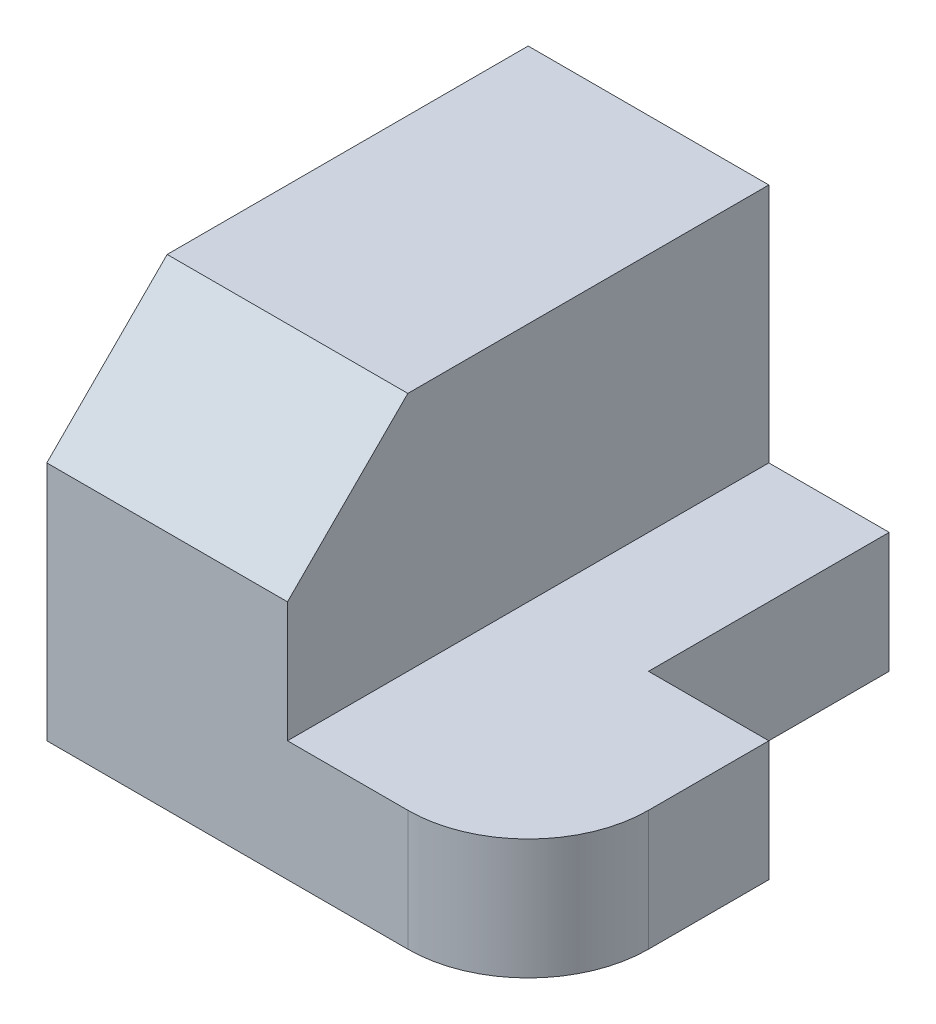
SolidWorks part; units mm, degrees
ref_plane "前基準面" through (0, 0, 0) normal (0, 0, 1) x (1, 0, 0)
ref_plane "上基準面" through (0, 0, 0) normal (0, 1, 0) x (1, 0, 0)
ref_plane "右基準面" through (0, 0, 0) normal (1, 0, 0) x (0, 0, -1)
sketch "草圖1" plane through (0, 0, 0) normal (0, 1, 0) x (1, 0, 0)
  line L1 (5, 10) -> (-5, 10)
  line L2 (5, 10) -> (5, -10)
  line L3 (5, -10) -> (-5, -10)
  line L4 (-5, 10) -> (-5, -10)
  line L5 (5, 10) -> (-5, -10) construction
  line L6 (5, -10) -> (-5, 10) construction
  line L7 (5, 10) -> (10, 10)
  line L8 (5, 10) -> (5, -10)
  line L9 (5, -10) -> (10, -10)
  line L10 (15, 0) -> (15, -5)
  line L13 (15, 0) -> (10, 0)
  line L14 (10, 10) -> (10, 0)
  line L15 (5, -10) -> (-5, -10)
  line L16 (5, -10) -> (5, -5)
  line L17 (5, -5) -> (-5, -5)
  line L18 (-5, -10) -> (-5, -5)
  arc A0 (15, -5) -> (10, -10) centre (10, -5) cw
  point P0 (0, 0)
  dimension "D7" = 5
  dimension "D1" = 20
  dimension "D2" = 10
  dimension "D3" = 10
  dimension "D4" = 5
  dimension "D5" = 10
  dimension "D6" = 5
extrude "填料-伸長1" add sketch "草圖1" along normal blind 5 contours A0 L10 L13 L14 L7 L2 L8 L9 region at (8.9917, 0, 1.399)
extrude "填料-伸長2" add sketch "草圖1<3>" along normal blind 15 contours L17 L2 L1 L4 | L8 L17 L4 L3 region at (0, 0, -2.5) region at (0, 0, 7.5)
sketch "草圖1<3>" plane through (0, 0, 0) normal (0, 1, 0) x (1, 0, 0) same geometry as "草圖1"
sketch "草圖2" plane through (-5, 0, 0) normal (-1, 0, 0) x (0, 0, 1)
  line L0 (5, 15) -> (10, 10)
  line L1 (-10, 15) -> (10, 15) construction
  line L2 (10, 15) -> (10, 0) construction
  line L3 (10, 10) -> (10, 15)
  line L4 (10, 15) -> (5, 15)
  dimension "D1" = 5
  dimension "D2" = 5
extrude "除料-伸長1" cut sketch "草圖2" against normal blind 15
scale "縮放比例1" scale about centroid uniform scaling yes scale factor 0.2
